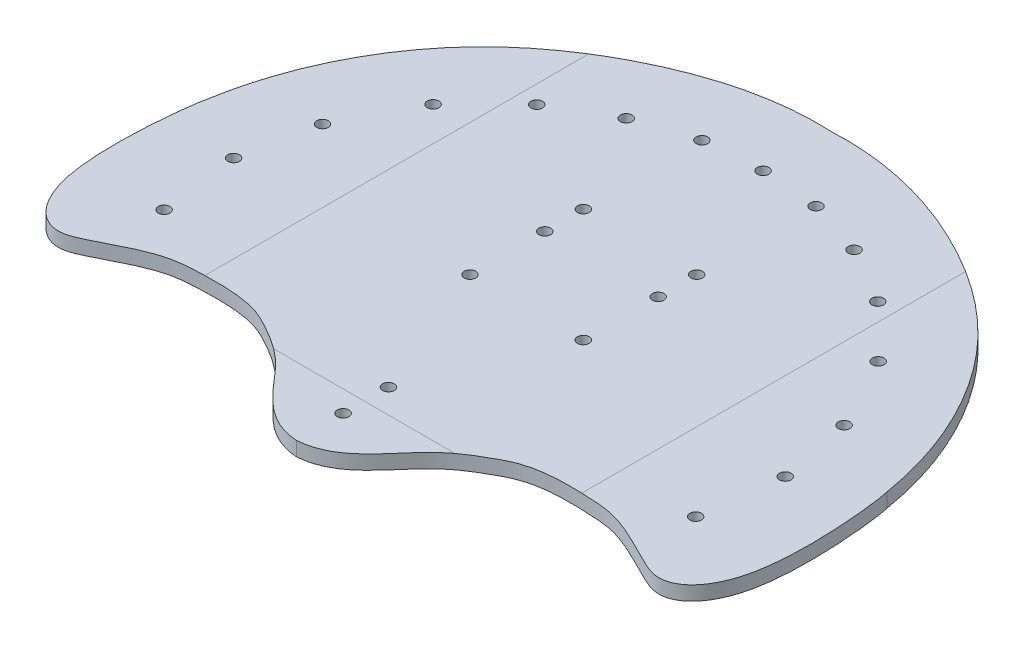
SolidWorks part; units mm, degrees
material "6061-T6 (SS)"
ref_plane "Front Plane" through (0, 0, 0) normal (0, 0, 1) x (1, 0, 0)
ref_plane "Top Plane" through (0, 0, 0) normal (0, 1, 0) x (1, 0, 0)
ref_plane "Right Plane" through (0, 0, 0) normal (1, 0, 0) x (0, 0, -1)
sketch "Sketch3" plane through (0, 0, 0) normal (0, 1, 0) x (1, 0, 0)
  line L0 (0, 0) -> (0, 159.1899) construction
  line L1 (0, 0) -> (0, -140.5301) construction
  line L2 (0, 0) -> (-190.5, 0) construction
  line L3 (0, 0) -> (190.5, 0) construction
  spline S0 degree 3 poles (-190.5, 0) (-184.3927, 37.537) (-157.2613, 93.9641) (-82.3875, 146.6227) (-31.3114, 160.7999) (0, 159.1899) knots 0 0 0 0 0.424401 0.65637 1 1 1 1
  spline S1 degree 3 poles (-190.5, 0) (-192.064, -4.9635) (-201.9672, -83.3146) (-174.6966, -109.29) (-151.6301, -100.568) (-131.4108, -87.7198) (-96.8436, -85.3754) (-78.6925, -86.2588) (-58.8335, -96.8794) (-37.3059, -109.9358) (-21.3496, -139.1148) (0, -140.5301) knots 0 0 0 0 0.166997 0.292321 0.319633 0.426735 0.458914 0.609242 0.64191 0.766802 1 1 1 1
  spline S2 degree 3 poles (190.5, 0) (192.064, -4.9635) (201.9672, -83.3146) (174.6966, -109.29) (151.6301, -100.568) (131.4108, -87.7198) (96.8436, -85.3754) (78.6925, -86.2588) (58.8335, -96.8794) (37.3059, -109.9358) (21.3496, -139.1148) (0, -140.5301) knots 0 0 0 0 0.166997 0.292321 0.319633 0.426735 0.458914 0.609242 0.64191 0.766802 1 1 1 1
  spline S3 degree 3 poles (190.5, 0) (184.3927, 37.537) (157.2613, 93.9641) (82.3875, 146.6227) (31.3114, 160.7999) (0, 159.1899) knots 0 0 0 0 0.424401 0.65637 1 1 1 1
  dimension "D1" = 381
  dimension "D2" = 299.72
  dimension "D3" = 159.1899
  dimension "D4" = 86.8953
  dimension "D5" = 104.4979
  dimension "D6" = 29.1616
  dimension "D7" = 92.2742
  dimension "D8" = 108.411
  dimension "D9" = 67.4883
  dimension "D10" = 43.7314
  dimension "D11" = 117.6915
  dimension "D12" = 162.2568
  dimension "D13" = 89.4522
  dimension "D14" = 140.1036
  dimension "D15" = 175.0666
  dimension "D16" = 50.2669
  dimension "D17" = 101.3666
  dimension "D18" = 138.1225
  dimension "D19" = 155.1557
  dimension "D20" = 192.0074
  dimension "D21" = 193.9268
  dimension "D23" = 76.6666
extrude "Boss-Extrude1" add sketch "Sketch3" along normal blind 7.9502 from surface starting at plane "Top Plane"
sketch "Sketch5" plane through (0, 0, 0) normal (0, -1, 0) x (1, 0, 0)
  line L0 (0, 0) -> (0, -20.32) construction
  line L1 (31.75, -52.07) -> (-31.75, -52.07)
  line L2 (31.75, -52.07) -> (31.75, 11.43)
  line L3 (31.75, 11.43) -> (-31.75, 11.43)
  line L4 (-31.75, -52.07) -> (-31.75, 11.43)
  line L5 (31.75, -52.07) -> (-31.75, 11.43) construction
  line L6 (31.75, 11.43) -> (-31.75, -52.07) construction
  line L7 (-31.75, -52.07) -> (-31.75, -30.48)
  line L8 (-31.75, -30.48) -> (31.75, -30.48) construction
  line L9 (0, -20.32) -> (140.7253, -20.32) construction
  line L10 (0, -20.32) -> (0, -97.1287) construction
  line L11 (0, -20.32) -> (31.9753, -118.7297) construction
  line L13 (0, -20.32) -> (63.8443, -108.1942) construction
  line L14 (0, -20.32) -> (95.5392, -89.7333) construction
  line L15 (124.7166, -60.8429) -> (0, -20.32) construction
  line L16 (0, -20.32) -> (154.5508, 21.0918) construction
  line L17 (0, -20.32) -> (148.922, 65.6601) construction
  line L18 (0, -20.32) -> (-31.9753, -118.7297) construction
  line L19 (0, -20.32) -> (-63.8443, -108.1942) construction
  line L20 (0, -20.32) -> (-95.5392, -89.7333) construction
  line L21 (-124.7166, -60.8429) -> (0, -20.32) construction
  line L22 (0, -20.32) -> (-154.5508, 21.0918) construction
  line L23 (0, -20.32) -> (-148.922, 65.6601) construction
  spline S0 degree 3 poles (-148.922, 65.6601) (-157.8584, 40.2253) (-156.2837, 8.5854) (-143.1202, -28.9506) (-139.3242, -37.3463) (-130.3709, -53.1962) (-125.215, -60.649) (-118.0488, -69.1403) (-116.5795, -70.7975) (-113.5719, -74.0252) (-112.0368, -75.592) (-107.2801, -80.2116) (-103.9215, -83.1695) (-93.3361, -91.6595) (-85.5959, -96.8074) (-76.3408, -101.9556) (-75.3049, -102.5187) (-73.219, -103.6268) (-72.1677, -104.1726) (-69.0049, -105.7765) (-66.8862, -106.8006) (-60.5068, -109.7299) (-56.2231, -111.4921) (-47.6308, -114.6027) (-43.3223, -115.9511) (-34.7104, -118.209) (-30.4072, -119.1185) (-21.8242, -120.4791) (-17.5446, -120.9304) (-11.1443, -121.2499) (-9.0138, -121.2968) (-5.8216, -121.2757) (-4.1848, -121.2414) (-2.5489, -121.1705) (-1.9677, -121.1408) (-1.9605, -121.1404) (-1.2995, -121.1064) (-0.6497, -121.073) (0, -121.0396) knots -0.292878 -0.292878 -0.292878 -0.292878 0.125 0.125 0.25 0.25 0.375 0.375 0.40625 0.40625 0.4375 0.4375 0.5 0.5 0.625 0.625 0.640625 0.640625 0.65625 0.65625 0.6875 0.6875 0.75 0.75 0.8125 0.8125 0.875 0.875 0.9375 0.9375 0.96875 0.96875 0.984375 0.992798 0.992798 0.99292 0.99292 1 1 1 1
  spline S5 degree 3 poles (998.6789, -69.6893) (665.1581, -86.8384) (331.6156, -103.9885) (-1.9268, -121.1387) (-1.9605, -121.1404) (-1.9677, -121.1408) (-2.5489, -121.1705) (-4.1848, -121.2414) (-5.8216, -121.2757) (-9.0138, -121.2968) (-11.1443, -121.2499) (-17.5446, -120.9304) (-21.8242, -120.4791) (-30.4072, -119.1185) (-34.7104, -118.209) (-43.3223, -115.9511) (-47.6308, -114.6027) (-56.2231, -111.4921) (-60.5068, -109.7299) (-66.8862, -106.8006) (-69.0049, -105.7765) (-72.1677, -104.1726) (-73.219, -103.6268) (-75.3049, -102.5187) (-76.3408, -101.9556) (-85.5959, -96.8074) (-93.3361, -91.6595) (-103.9215, -83.1695) (-107.2801, -80.2116) (-112.0368, -75.592) (-113.5719, -74.0252) (-116.5795, -70.7975) (-118.0488, -69.1403) (-125.215, -60.649) (-130.3709, -53.1962) (-139.3242, -37.3463) (-143.1202, -28.9506) (-198.5095, 128.9933) (-22.362, 351.6373) (651.8169, -587.5188) knots -3.627409 -3.627409 -3.627409 -3.627409 0.006836 0.00708 0.00708 0.007202 0.007202 0.015625 0.03125 0.03125 0.0625 0.0625 0.125 0.125 0.1875 0.1875 0.25 0.25 0.3125 0.3125 0.34375 0.34375 0.359375 0.359375 0.375 0.375 0.5 0.5 0.5625 0.5625 0.59375 0.59375 0.625 0.625 0.75 0.75 0.875 0.875 3.034324 3.034324 3.034324 3.034324 only from (0, -121.0396) to (-152.8945, 6.1184)
  spline S6 degree 3 poles (-1687.8289, -2297.0686) (-150.4269, 537.0593) (218.9922, 187.4002) (143.1202, -28.9506) (139.3242, -37.3463) (130.3709, -53.1962) (125.215, -60.649) (118.0488, -69.1403) (116.5795, -70.7975) (113.5719, -74.0252) (112.0368, -75.592) (107.2801, -80.2116) (103.9215, -83.1695) (93.3361, -91.6595) (85.5959, -96.8074) (76.3408, -101.9556) (75.3049, -102.5187) (73.219, -103.6268) (72.1677, -104.1726) (69.0049, -105.7765) (66.8862, -106.8006) (60.5068, -109.7299) (56.2231, -111.4921) (47.6308, -114.6027) (43.3223, -115.9511) (34.7104, -118.209) (30.4072, -119.1185) (21.8242, -120.4791) (17.5446, -120.9304) (11.1443, -121.2499) (9.0138, -121.2968) (5.8216, -121.2757) (4.1848, -121.2414) (2.5489, -121.1705) (1.9677, -121.1408) (1.9605, -121.1404) (-997.3522, -69.7575) (-1996.6535, -18.3753) (-2996.029, 33.0152) knots -2.879056 -2.879056 -2.879056 -2.879056 0.125 0.125 0.25 0.25 0.375 0.375 0.40625 0.40625 0.4375 0.4375 0.5 0.5 0.625 0.625 0.640625 0.640625 0.65625 0.65625 0.6875 0.6875 0.75 0.75 0.8125 0.8125 0.875 0.875 0.9375 0.9375 0.96875 0.96875 0.984375 0.992798 0.992798 0.99292 0.99292 11.881939 11.881939 11.881939 11.881939 only from (152.8945, 6.1184) to (0, -121.0396)
  spline S8 degree 3 poles (148.922, 65.6601) (157.8584, 40.2253) (156.2837, 8.5854) (143.1202, -28.9506) (139.3242, -37.3463) (130.3709, -53.1962) (125.215, -60.649) (118.0488, -69.1403) (116.5795, -70.7975) (113.5719, -74.0252) (112.0368, -75.592) (107.2801, -80.2116) (103.9215, -83.1695) (93.3361, -91.6595) (85.5959, -96.8074) (76.3408, -101.9556) (75.3049, -102.5187) (73.219, -103.6268) (72.1677, -104.1726) (69.0049, -105.7765) (66.8862, -106.8006) (60.5068, -109.7299) (56.2231, -111.4921) (47.6308, -114.6027) (43.3223, -115.9511) (34.7104, -118.209) (30.4072, -119.1185) (21.8242, -120.4791) (17.5446, -120.9304) (11.1443, -121.2499) (9.0138, -121.2968) (5.8216, -121.2757) (4.1848, -121.2414) (2.5489, -121.1705) (1.9677, -121.1408) (1.9605, -121.1404) (1.2995, -121.1064) (0.6497, -121.073) (0, -121.0396) knots -0.292878 -0.292878 -0.292878 -0.292878 0.125 0.125 0.25 0.25 0.375 0.375 0.40625 0.40625 0.4375 0.4375 0.5 0.5 0.625 0.625 0.640625 0.640625 0.65625 0.65625 0.6875 0.6875 0.75 0.75 0.8125 0.8125 0.875 0.875 0.9375 0.9375 0.96875 0.96875 0.984375 0.992798 0.992798 0.99292 0.99292 1 1 1 1
  point P0 (0, -20.32)
  point P3 (0, -20.32)
  point P14 (0, 114.3)
  point P16 (0, 88.9)
  dimension "D2" = 63.5
  dimension "D3" = 63.5
  dimension "D4" = 21.59
  dimension "D6" = 25.4
  dimension "D7" = 88.9
  dimension "D8" = 18
  dimension "D9" = 18
  dimension "D10" = 18
  dimension "D11" = 18
  dimension "D12" = 15
  dimension "D13" = 15
  dimension "D5" = 38.1
hole_wizard "F (0.257) Diameter Hole2" positions "Sketch6" profile "Sketch7" hole size "F" standard "ANSI Inch" end condition through all
sketch "Sketch6" plane through (0, 0, 0) normal (0, -1, 0) x (-1, 0, 0)
  line L0 (200000, 20.32) -> (-200140.7253, 20.32) construction
  spline S0 degree 3 poles (-148.922, -65.6601) (-157.8584, -40.2253) (-156.2837, -8.5854) (-143.1202, 28.9506) (-139.3242, 37.3463) (-130.3709, 53.1962) (-125.215, 60.649) (-118.0488, 69.1403) (-116.5795, 70.7975) (-113.5719, 74.0252) (-112.0368, 75.592) (-107.2801, 80.2116) (-103.9215, 83.1695) (-93.3361, 91.6595) (-85.5959, 96.8074) (-76.3408, 101.9556) (-75.3049, 102.5187) (-73.219, 103.6268) (-72.1677, 104.1726) (-69.0049, 105.7765) (-66.8862, 106.8006) (-60.5068, 109.7299) (-56.2231, 111.4921) (-47.6308, 114.6027) (-43.3223, 115.9511) (-34.7104, 118.209) (-30.4072, 119.1185) (-21.8242, 120.4791) (-17.5446, 120.9304) (-11.1443, 121.2499) (-9.0138, 121.2968) (-5.8216, 121.2757) (-4.1848, 121.2414) (-2.5489, 121.1705) (-1.9677, 121.1408) (-1.9605, 121.1404) (-1.2995, 121.1064) (-0.6497, 121.073) (0, 121.0396) knots -0.292878 -0.292878 -0.292878 -0.292878 0.125 0.125 0.25 0.25 0.375 0.375 0.40625 0.40625 0.4375 0.4375 0.5 0.5 0.625 0.625 0.640625 0.640625 0.65625 0.65625 0.6875 0.6875 0.75 0.75 0.8125 0.8125 0.875 0.875 0.9375 0.9375 0.96875 0.96875 0.984375 0.992798 0.992798 0.99292 0.99292 1 1 1 1 construction
  spline S1 degree 3 poles (148.922, -65.6601) (157.8584, -40.2253) (156.2837, -8.5854) (143.1202, 28.9506) (139.3242, 37.3463) (130.3709, 53.1962) (125.215, 60.649) (118.0488, 69.1403) (116.5795, 70.7975) (113.5719, 74.0252) (112.0368, 75.592) (107.2801, 80.2116) (103.9215, 83.1695) (93.3361, 91.6595) (85.5959, 96.8074) (76.3408, 101.9556) (75.3049, 102.5187) (73.219, 103.6268) (72.1677, 104.1726) (69.0049, 105.7765) (66.8862, 106.8006) (60.5068, 109.7299) (56.2231, 111.4921) (47.6308, 114.6027) (43.3223, 115.9511) (34.7104, 118.209) (30.4072, 119.1185) (21.8242, 120.4791) (17.5446, 120.9304) (11.1443, 121.2499) (9.0138, 121.2968) (5.8216, 121.2757) (4.1848, 121.2414) (2.5489, 121.1705) (1.9677, 121.1408) (1.9605, 121.1404) (1.2995, 121.1064) (0.6497, 121.073) (0, 121.0396) knots -0.292878 -0.292878 -0.292878 -0.292878 0.125 0.125 0.25 0.25 0.375 0.375 0.40625 0.40625 0.4375 0.4375 0.5 0.5 0.625 0.625 0.640625 0.640625 0.65625 0.65625 0.6875 0.6875 0.75 0.75 0.8125 0.8125 0.875 0.875 0.9375 0.9375 0.96875 0.96875 0.984375 0.992798 0.992798 0.99292 0.99292 1 1 1 1 construction
  point P3 (31.75, 52.07)
  point P6 (31.75, -11.43)
  point P9 (-31.75, -11.43)
  point P15 (31.75, 30.48)
  point P32 (-31.75, 30.48)
  point P39 (-31.75, 52.07)
  point P42 (-154.5508, -21.0918)
  point P45 (-148.922, -65.6601)
  point P48 (-146.1469, 20.32)
  point P54 (-124.7166, 60.8429)
  point P57 (-95.5392, 89.7333)
  point P60 (148.922, -65.6601)
  point P63 (154.5508, -21.0918)
  point P66 (124.7166, 60.8429)
  point P69 (95.5392, 89.7333)
  point P72 (63.8443, 108.1942)
  point P76 (31.9753, 118.7297)
  point P79 (0, 121.0396)
  point P82 (-31.9753, 118.7297)
  point P85 (-63.8443, 108.1942)
  point P88 (-95.5392, 89.7333)
  point P91 (146.1469, 20.32)
  point P95 (0, -88.9)
  point P98 (0, -114.3)
sketch "Sketch7" plane through (-31.75, 0, -52.07) normal (1, 0, 0) x (0, 0, -1)
  line L0 (0, 0) -> (0, 7.9502)
  line L1 (0, 7.9502) -> (3.2639, 7.9502)
  line L2 (3.2639, 7.9502) -> (3.2639, 0)
  line L5 (3.2639, 0) -> (0, 0)
  line L11 (0, -6.35) -> (0, 107.95) construction
  dimension "Thru Hole Dia." = 6.5278
  dimension "Thru Hole Depth" = 7.9502
sketch "Sketch9" plane through (0, 7.9502, 0) normal (0, 1, 0) x (1, 0, 0)
  line L0 (105.6044, -86.1614) -> (105.6044, 128.9378)
  line L1 (-50.7649, -102.4301) -> (50.7649, -102.4301)
  line L2 (0, 0) -> (0, 108.4804) construction
  line L3 (194.5044, -48.0614) -> (105.6044, -48.0614) construction
  line L4 (148.922, -65.6601) -> (193.6656, -65.6601) construction
  line L5 (-105.6044, -86.1614) -> (-105.6044, 128.9378)
  spline S0 degree 3 poles (0, -140.5301) (21.3496, -139.1148) (37.3059, -109.9358) (58.8335, -96.8794) (78.6925, -86.2588) (96.8436, -85.3754) (131.4108, -87.7198) (151.6301, -100.568) (174.6966, -109.29) (201.9672, -83.3146) (192.064, -4.9635) (190.5, 0) knots 0 0 0 0 0.233198 0.35809 0.390758 0.541086 0.573265 0.680367 0.707679 0.833003 1 1 1 1 construction
  spline S1 degree 3 poles (190.5, 0) (184.3927, 37.537) (157.2613, 93.9641) (82.3875, 146.6227) (31.3114, 160.7999) (0, 159.1899) knots 0 0 0 0 0.424401 0.65637 1 1 1 1 construction
  spline S2 degree 3 poles (-190.5, 0) (-192.064, -4.9635) (-201.9672, -83.3146) (-174.6966, -109.29) (-151.6301, -100.568) (-131.4108, -87.7198) (-96.8436, -85.3754) (-78.6925, -86.2588) (-58.8335, -96.8794) (-37.3059, -109.9358) (-21.3496, -139.1148) (0, -140.5301) knots 0 0 0 0 0.166997 0.292321 0.319633 0.426735 0.458914 0.609242 0.64191 0.766802 1 1 1 1 construction
  point P21 (171.0944, -65.6601)
  dimension "D1" = 38.1
  dimension "D2" = 88.9
  dimension "D3" = 38.1
split line "Split Line1"
sketch "Sketch10" plane through (0, 0, 0) normal (0, -1, 0) x (1, 0, 0)
  line L0 (31.75, 11.43) -> (31.75, 24.13) construction
  line L1 (-31.75, 11.43) -> (31.75, 11.43) construction
  line L2 (-31.75, 11.43) -> (-31.75, -52.07) construction
  line L3 (-31.75, -52.07) -> (31.75, -52.07) construction
  line L4 (31.75, 11.43) -> (31.75, -52.07) construction
  line L5 (-44.45, 24.13) -> (44.45, 24.13)
  line L6 (-44.45, 24.13) -> (-44.45, -64.77)
  line L7 (-44.45, -64.77) -> (44.45, -64.77)
  line L8 (44.45, 24.13) -> (44.45, -64.77)
  line L9 (31.75, 11.43) -> (44.45, 11.43) construction
  line L10 (-31.75, -52.07) -> (-44.45, -52.07) construction
  line L11 (-31.75, -52.07) -> (-31.75, -64.77) construction
  dimension "D1" = 88.9
split line "Split Line2"
equation "\"Plate thickness\"=0.313"
equation "\"D1@Boss-Extrude1\"=\"Plate thickness\""
equation "\"Bracket Alignment\"= .80"
equation "\"D1@Sketch5\"=\"Bracket Alignment\""
